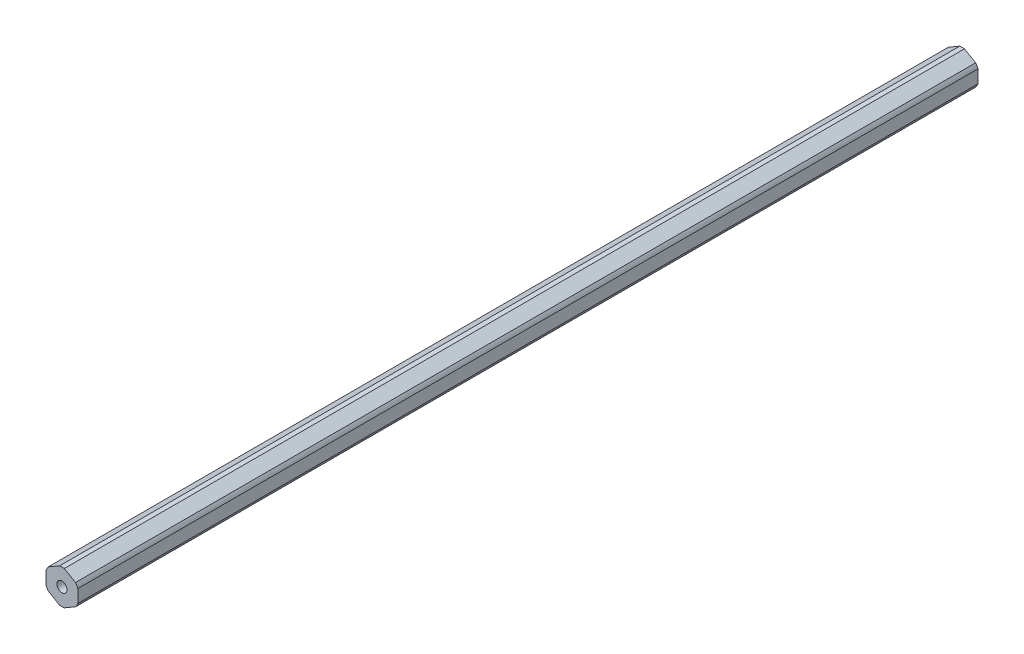
SolidWorks part; units mm, degrees
material "7075-T6 (SN)"
ref_plane "Front Plane" through (0, 0, 0) normal (0, 0, 1) x (1, 0, 0)
ref_plane "Top Plane" through (0, 0, 0) normal (0, 1, 0) x (1, 0, 0)
ref_plane "Right Plane" through (0, 0, 0) normal (1, 0, 0) x (0, 0, -1)
sketch "Sketch1" plane through (0, 0, 0) normal (0, 0, 1) x (1, 0, 0)
  line L7 (6.35, 3.6662) -> (0, 7.3323)
  line L8 (0, 7.3323) -> (-6.35, 3.6662)
  line L9 (-6.35, 3.6662) -> (-6.35, -3.6662)
  line L10 (-6.35, -3.6662) -> (0, -7.3323)
  line L11 (0, -7.3323) -> (6.35, -3.6662)
  line L12 (6.35, -3.6662) -> (6.35, 3.6662)
  circle A0 centre (0, 0) radius 6.35 construction
  circle A2 centre (0, 0) radius 6.858
  dimension "D1" = 12.7
  dimension "D2" = 13.716
extrude "Boss-Extrude1" add sketch "Sketch1" along normal mid plane 359.029 contours L12 A2 L7 L8 L9 L10 L11 region at (0, 0, 0)
sketch "Sketch2" plane through (0, 0, 179.5145) normal (0, 0, 1) x (1, 0, 0)
  circle A0 centre (0, 0) radius 2.0193
  dimension "D1" = 4.0386
extrude "Cut-Extrude1" cut sketch "Sketch2" against normal through all
